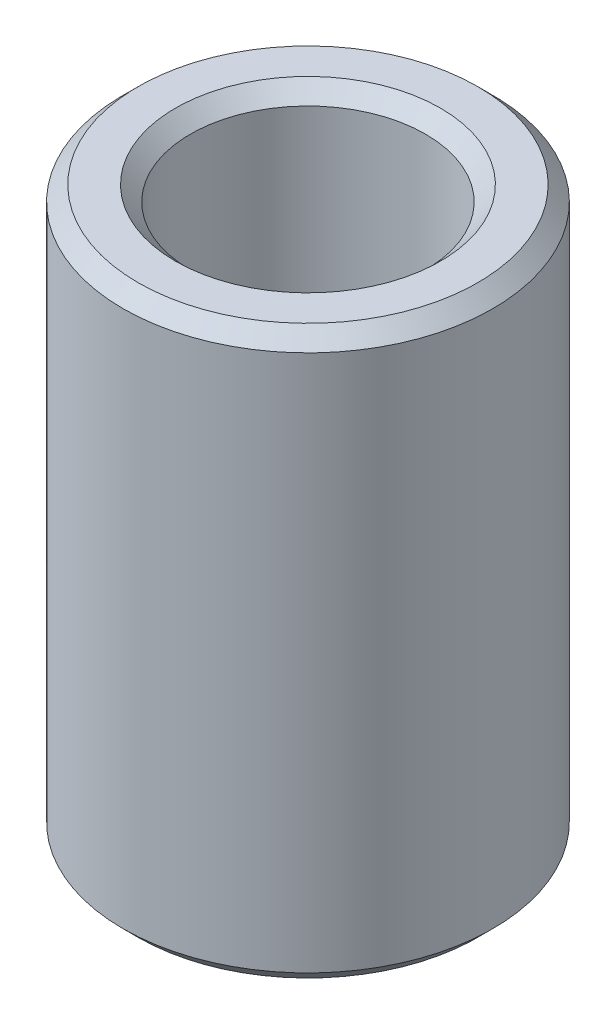
SolidWorks part; units mm, degrees
ref_plane "Front Plane" through (0, 0, 0) normal (0, 0, 1) x (1, 0, 0)
ref_plane "Top Plane" through (0, 0, 0) normal (0, 1, 0) x (1, 0, 0)
ref_plane "Right Plane" through (0, 0, 0) normal (1, 0, 0) x (0, 0, -1)
sketch "Sketch1" plane through (0, 0, 0) normal (0, 1, 0) x (1, 0, 0)
  circle A0 centre (0, 0) radius 42.5
  dimension "SLEEVE_OD" = 85
extrude "Boss-Extrude1" add sketch "Sketch1" along normal blind 130.3668
sketch "Sketch2" plane through (0, 0, 0) normal (0, 1, 0) x (1, 0, 0)
  circle A0 centre (0, 0) radius 27.0292
  dimension "BORE_D" = 54.0584
extrude "Cut-Extrude1" cut sketch "Sketch2" along normal through all
chamfer "Chamfer1" distance 3.45 angle 45 4 edges at (0, 130.3668, 27.0292) (0, 0, 27.0292) (0, 0, 42.5) (0, 130.3668, 42.5)
